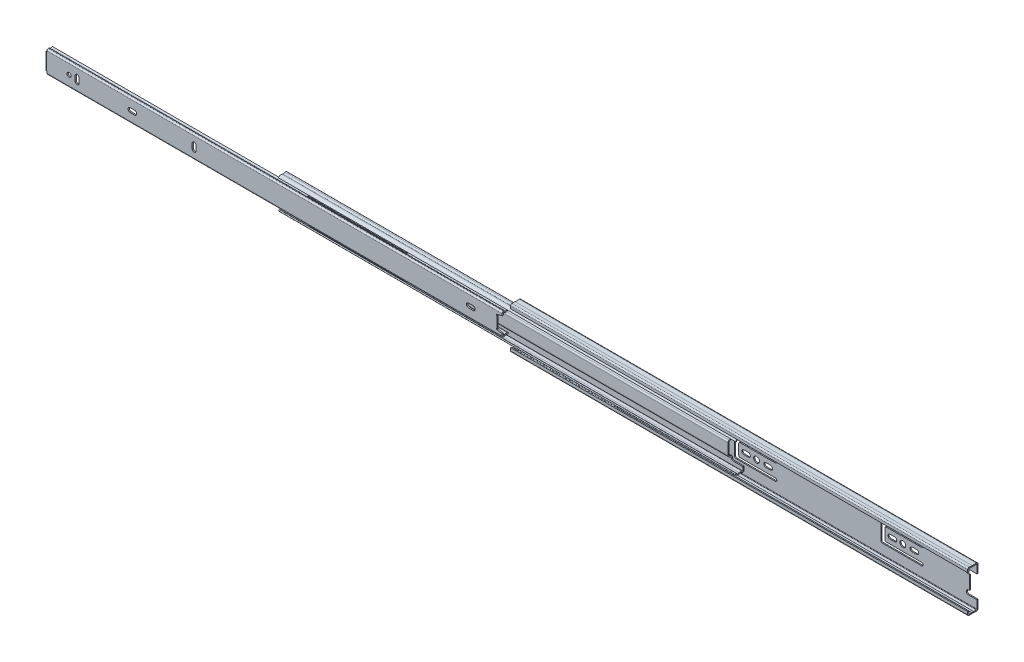
SolidWorks part; units mm, degrees
ref_plane "Front" through (0, 0, 0) normal (0, 0, 1) x (1, 0, 0)
ref_plane "Top" through (0, 0, 0) normal (0, 1, 0) x (1, 0, 0)
ref_plane "Right" through (0, 0, 0) normal (1, 0, 0) x (0, 0, -1)
sketch "Sketch1" plane through (0, 0, 0) normal (1, 0, 0) x (0, 0, -1)
  line L1 (5.6388, 0) -> (-5.6388, 0) construction
  line L4 (-4.1393, 22.8203) -> (-0.7433, 22.6989)
  line L5 (-1.1312, 21.5182) -> (-4.1819, 21.6273)
  line L6 (-4.445, 18.415) -> (-5.6388, 18.415)
  line L7 (-4.445, 21.3734) -> (-4.445, 18.415)
  line L8 (-5.6388, 18.415) -> (-5.6388, 21.3734)
  line L9 (3.9237, 21.6269) -> (0.7619, 21.5441)
  line L10 (5.6388, 0) -> (5.6388, 21.1191)
  line L11 (4.445, 21.1191) -> (4.445, 0)
  line L12 (5.6388, 0) -> (4.445, 0)
  line L13 (-0.7433, 22.6989) -> (3.8925, 22.8203)
  arc A0 (-4.445, 21.3734) -> (-4.1819, 21.6273) centre (-4.191, 21.3734) cw
  arc A1 (-5.6388, 21.3734) -> (-4.1393, 22.8203) centre (-4.191, 21.3734) cw
  arc A3 (3.9237, 21.6269) -> (4.445, 21.1191) centre (3.937, 21.1191) cw
  arc A4 (3.8925, 22.8203) -> (5.6388, 21.1191) centre (3.937, 21.1191) cw
  arc A5 (-1.1312, 21.5182) -> (0.7619, 21.5441) centre (-0.1524, 19.1744) cw
  dimension "D2" = 19.1744
  dimension "D7" = 0.254
  dimension "D8" = 0.508
  dimension "D6" = 2.54
  dimension "D9" = 1.1938
  dimension "D10" = 88.5
  dimension "D1" = 11.2776
  dimension "D3" = 5.7912
  dimension "D4" = 36.83
  dimension "D5" = 1.1938
  dimension "D11" = 87.953
  dimension "D12" = 45.6406
extrude "Extrude1" add sketch "Sketch1" along normal mid plane 500.126
ref_plane "Travel / 2" through (-504.063, 0, 0) normal (-1, 0, 0) x (0, 0, 1)
sketch "Sketch2" plane through (-504.063, 0, 0) normal (-1, 0, 0) x (0, 0, 1)
  line L0 (0.0254, 6.1159) -> (0.0254, 0)
  line L2 (-5.6388, 0) -> (5.6388, 0) construction
  line L3 (5.6388, 21.3734) -> (5.6388, 18.415) construction
  line L7 (-4.445, 21.1191) -> (-4.445, 0) construction
  line L8 (-5.6388, 0) -> (-5.6388, 21.1191) construction
  line L13 (-3.5306, 16.3766) -> (-3.5306, 9.5217)
  line L46 (-2.3867, 7.7262) -> (-0.4146, 6.8065)
  arc A0 (0.0254, 6.1159) -> (-0.4146, 6.8065) centre (-0.7366, 6.1159) ccw
  arc A1 (-1.5056, 17.2916) -> (1.2415, 16.9143) centre (0.1524, 19.1744) ccw
  arc A4 (1.1312, 21.5182) -> (-0.7619, 21.5441) centre (0.1524, 19.1744) ccw construction
  arc A19 (-3.5306, 9.5217) -> (-2.3867, 7.7262) centre (-1.5494, 9.5217) ccw
  arc A25 (-1.5056, 17.2916) -> (-3.5306, 16.3766) centre (-2.3114, 16.3766) ccw
  arc A51 (5.7404, 15.6277) -> (1.2415, 16.9143) centre (2.7686, 13.7451) ccw
  dimension "D2" = 8.4074
  dimension "D3" = 27.4903
  dimension "D6" = 1.9812
  dimension "D8" = 12.2319
  dimension "D10" = 2.5088
  dimension "D11" = 1.2192
  dimension "D4" = 0.762
  dimension "D5" = 4.4704
  dimension "D7" = 115
  dimension "D9" = 19.0435
  dimension "D13" = 11.3792
extrude "Middle Member" add sketch "Sketch2" against normal blind 500.126 separate body thin thin type one direction reverse wall 1.2192
ref_plane "Travel" through (-758.063, 0, 0) normal (-1, 0, 0) x (0, 0, 1)
sketch "Sketch3" plane through (-758.063, 0, 0) normal (-1, 0, 0) x (0, 0, 1)
  line L0 (1.2446, 0) -> (0.0254, 0) construction
  line L1 (-5.6388, 0) -> (-5.6388, 21.1191) construction
  line L56 (7.0612, 0) -> (7.0612, 10.6235)
  line L93 (5.5372, 12.1475) -> (5.1643, 12.1475)
  arc A0 (1.2082, 11.9072) -> (4.2365, 11.8325) centre (2.7686, 13.7451) ccw
  arc A29 (7.0612, 10.6235) -> (5.5372, 12.1475) centre (5.5372, 10.6235) ccw
  arc A53 (5.1643, 12.1475) -> (4.2365, 11.8325) centre (5.1643, 10.6235) ccw
  dimension "D1" = 1.524
  dimension "D4" = 1.524
  dimension "D5" = 2.411
  dimension "D2" = 12.7
  dimension "D3" = 12.1475
  dimension "D6" = 5.853
extrude "Drawer Member" add sketch "Sketch3" against normal blind 500.126 thin thin type one direction wall 1.397
sketch "Sketch6" plane through (0, 0, 7.0612) normal (0, 0, 1) x (1, 0, 0)
  line L1 (-758.063, 0) -> (-756.158, 0)
  line L2 (-758.063, 0) -> (-758.063, 12.1475)
  line L3 (-758.063, 12.1475) -> (-756.158, 12.1475)
  line L4 (-756.158, 0) -> (-756.158, 12.1475)
  line L5 (-257.937, 12.1475) -> (-758.063, 12.1475) construction
  line L7 (-758.063, 10.6235) -> (-758.063, 0) construction
  line L8 (-257.937, 0) -> (-758.063, 0) construction
  dimension "D1" = 1.905
extrude "Cut-Extrude1" cut sketch "Sketch6" against normal through all
sketch "Sketch7" plane through (0, 0, 0) normal (0, -1, 0) x (1, 0, 0)
  line L0 (-756.158, 7.0612) -> (-756.412, 7.0612)
  line L1 (-758.063, 5.4102) -> (-758.063, 0.3041)
  line L2 (-758.063, 0.3041) -> (-756.666, 0.3041)
  line L3 (-756.666, 0.3041) -> (-756.666, 5.4102)
  line L4 (-756.412, 5.6642) -> (-756.158, 5.6642)
  line L5 (-257.937, 5.6642) -> (-756.158, 5.6642) construction
  line L6 (-756.158, 7.0612) -> (-756.158, 5.6642)
  line L7 (-257.937, 0.3041) -> (-756.158, 0.3041) construction
  line L9 (-756.158, 5.087) -> (-756.158, 0.3041) construction
  arc A0 (-756.412, 5.6642) -> (-756.666, 5.4102) centre (-756.412, 5.4102) ccw
  arc A1 (-756.412, 7.0612) -> (-758.063, 5.4102) centre (-756.412, 5.4102) ccw
  dimension "D1" = 0.254
  dimension "D2" = 1.905
extrude "Extrude4" add sketch "Sketch7" against normal blind 8.89
sketch "Sketch8" plane through (0, 0, -4.445) normal (0, 0, 1) x (1, 0, 0)
  line L0 (240.4245, 7.6456) -> (241.8588, 7.493)
  line L1 (250.063, 12.2048) -> (240.6664, 12.2048)
  line L2 (241.8588, 7.493) -> (241.8588, 0)
  line L3 (250.063, 0) -> (-250.063, 0) construction
  line L4 (250.063, 21.1191) -> (250.063, 0) construction
  line L5 (250.063, 12.2048) -> (250.063, 0)
  line L6 (250.063, 0) -> (241.8588, 0)
  arc A0 (240.6664, 12.2048) -> (240.4245, 7.6456) centre (240.6664, 9.9188) ccw
  dimension "D3" = 9.9188
  dimension "D1" = 12.2048
  dimension "D2" = 8.2042
  dimension "D4" = 9.3966
  dimension "D5" = 7.493
extrude "Cut-Extrude2" cut sketch "Sketch8" against normal up to next (1.1938 mm away)
sketch "Sketch11" plane through (0, 0, 7.0612) normal (0, 0, 1) x (1, 0, 0)
  line L0 (-263.652, 5.9678) -> (-263.652, 0)
  line L8 (-257.937, 8.5893) -> (-263.7963, 7.2212)
  line L11 (-263.652, 0) -> (-257.937, 0)
  line L12 (-257.937, 0) -> (-257.937, 8.5893)
  arc A1 (-263.7963, 7.2212) -> (-263.652, 5.9678) centre (-263.6519, 6.6028) ccw
  dimension "D3" = 0.635
  dimension "D1" = 5.715
  dimension "D2" = 8.5893
  dimension "D4" = 5.9678
  dimension "D5" = 103.143
extrude "Cut-Extrude3" cut sketch "Sketch11" against normal up to next (1.397 mm away)
sketch "Sketch12" plane through (0, 0, 1.2446) normal (0, 0, 1) x (1, 0, 0)
  line L0 (-3.937, 12.065) -> (-14.097, 12.065)
  line L1 (-3.937, 16.3766) -> (-3.937, 9.5217) construction
  line L2 (-16.637, 9.525) -> (-16.637, 0)
  line L3 (-3.937, 0) -> (-504.063, 0) construction
  line L4 (-16.637, 0) -> (-3.937, 0)
  line L5 (-3.937, 0) -> (-3.937, 12.065)
  arc A0 (-14.097, 12.065) -> (-16.637, 9.525) centre (-14.097, 9.525) ccw
  point P11 (-16.637, 12.065)
  dimension "D3" = 2.54
  dimension "D1" = 12.7
  dimension "D2" = 12.065
extrude "Cut-Extrude4" cut sketch "Sketch12" against normal through all
sketch "Sketch13" plane through (0, 0, -4.445) normal (0, 0, 1) x (1, 0, 0)
  line L0 (-181.6747, 7.112) -> (-206.5032, 7.112)
  line L1 (241.8588, 0) -> (-250.063, 0) construction
  line L2 (-189.7646, 0) -> (-189.7646, 4.2392) construction
  line L3 (-232.6017, 10.287) -> (-181.6747, 10.287)
  line L4 (-250.063, 21.1191) -> (-250.063, 0) construction
  line L5 (-210.3132, 7.112) -> (-232.6017, 7.112)
  line L6 (-209.5512, 0) -> (-209.5512, 6.35)
  line L7 (-207.2652, 6.35) -> (-207.2652, 0)
  line L8 (-187.2881, 2.286) -> (-192.2411, 2.286)
  line L13 (-226.3406, 0) -> (-221.7686, 0)
  line L14 (-218.238, 0) -> (-211.888, 0)
  line L15 (-209.5512, 0) -> (-207.2652, 0)
  line L16 (-204.7506, 0) -> (-200.1786, 0)
  line L17 (-194.5271, 0) -> (-185.0021, 0)
  arc A1 (-232.6017, 10.287) -> (-232.6017, 7.112) centre (-232.6017, 8.6995) ccw
  arc A2 (-209.5512, 6.35) -> (-210.3132, 7.112) centre (-210.3132, 6.35) ccw
  arc A4 (-206.5032, 7.112) -> (-207.2652, 6.35) centre (-206.5032, 6.35) ccw
  arc A7 (-181.6747, 7.112) -> (-181.6747, 10.287) centre (-181.6747, 8.6995) ccw
  arc A8 (-211.888, 0) -> (-218.238, 0) centre (-215.063, 0) ccw
  arc A9 (-221.7686, 0) -> (-226.3406, 0) centre (-224.0546, 0) ccw
  arc A10 (-200.1786, 0) -> (-204.7506, 0) centre (-202.4646, 0) ccw
  arc A11 (-185.0021, 0) -> (-187.2881, 2.286) centre (-187.2881, 0) ccw
  arc A12 (-192.2411, 2.286) -> (-194.5271, 0) centre (-192.2411, 0) ccw
  dimension "D3" = 2.286
  dimension "D4" = 3.175
  dimension "D7" = 8.9916
  dimension "D8" = 21.59
  dimension "D9" = 34.29
  dimension "D10" = 0.762
  dimension "D11" = 17.5387
  dimension "D12" = 9.525
  dimension "D13" = 5.5118
  dimension "D14" = 35
  dimension "D1" = 3.175
  dimension "D2" = 50.927
  dimension "D5" = 2.286
  dimension "D6" = 10.287
extrude "Cut-Extrude5" cut sketch "Sketch13" against normal up to next (1.1938 mm away)
sketch "Sketch32" plane through (0, 0, -5.6388) normal (0, 0, -1) x (-1, 0, 0)
  line L0 (69.6005, 0) -> (79.1255, 0)
  line L1 (83.888, 0) -> (90.238, 0)
  line L2 (93.7305, 0) -> (103.2555, 0)
  line L3 (106.621, 0) -> (111.193, 0)
  line L4 (-241.8588, 0) -> (185.0021, 0) construction
  line L5 (232.6017, 10.287) -> (181.6747, 10.287) construction
  line L6 (181.6747, 7.112) -> (206.5032, 7.112) construction
  line L7 (98.493, 2.286) -> (98.493, -3.4269) construction
  line L8 (74.363, 2.286) -> (74.363, -3.4269) construction
  line L14 (66.4255, 10.287) -> (109.669, 10.287)
  line L15 (105.097, 7.112) -> (66.4255, 7.112)
  line L17 (111.193, 8.763) -> (111.193, 0)
  line L18 (106.621, 0) -> (106.621, 5.588)
  line L23 (71.8865, 2.286) -> (76.8395, 2.286)
  line L25 (96.0165, 2.286) -> (100.9695, 2.286)
  arc A0 (218.238, 0) -> (211.888, 0) centre (215.063, 0) ccw construction
  arc A13 (111.193, 8.763) -> (109.669, 10.287) centre (109.669, 8.763) ccw
  arc A14 (106.621, 5.588) -> (105.097, 7.112) centre (105.097, 5.588) ccw
  arc A17 (66.4255, 10.287) -> (66.4255, 7.112) centre (66.4255, 8.6995) ccw
  arc A20 (79.1255, 0) -> (76.8395, 2.286) centre (76.8395, 0) ccw
  arc A21 (71.8865, 2.286) -> (69.6005, 0) centre (71.8865, 0) ccw
  arc A22 (90.238, 0) -> (83.888, 0) centre (87.063, 0) ccw
  arc A24 (103.2555, 0) -> (100.9695, 2.286) centre (100.9695, 0) ccw
  arc A25 (96.0165, 2.286) -> (93.7305, 0) centre (96.0165, 0) ccw
  dimension "D2" = 1.524
  dimension "D3" = 3.175
  dimension "D4" = 9.525
  dimension "D5" = 2.286
  dimension "D6" = 11.43
  dimension "D7" = 12.7
  dimension "D8" = 24.13
  dimension "D9" = 20.6375
  dimension "D10" = 128
  dimension "D1" = 4.572
extrude "Cut-Extrude14" cut sketch "Sketch32" against normal up to next (1.1938 mm away)
sketch "Sketch33" plane through (83.6094, 0.8125, -5.6388) normal (0, 0, -1) x (-1, 0, 0)
  line L0 (57.2099, -0.8125) -> (66.7349, -0.8125)
  line L1 (71.4974, -0.8125) -> (77.8474, -0.8125)
  line L2 (81.3399, -0.8125) -> (90.8649, -0.8125)
  line L3 (94.2304, -0.8125) -> (98.8024, -0.8125)
  line L7 (86.1024, 1.4735) -> (86.1024, -4.2394) construction
  line L8 (61.9724, 1.4735) -> (61.9724, -3.4269) construction
  line L9 (-158.2494, -0.8125) -> (153.2099, -0.8125) construction
  line L10 (193.2784, 9.4745) -> (150.0349, 9.4745) construction
  line L11 (150.0349, 6.2995) -> (188.7064, 6.2995) construction
  line L14 (54.0349, 9.4745) -> (97.2784, 9.4745)
  line L15 (92.7064, 6.2995) -> (54.0349, 6.2995)
  line L17 (98.8024, 7.9505) -> (98.8024, -0.8125)
  line L18 (94.2304, -0.8125) -> (94.2304, 4.7755)
  line L23 (59.4959, 1.4735) -> (64.4489, 1.4735)
  line L25 (83.6259, 1.4735) -> (88.5789, 1.4735)
  arc A1 (301.8474, -0.8125) -> (295.4974, -0.8125) centre (298.6724, -0.8125) ccw construction
  arc A13 (98.8024, 7.9505) -> (97.2784, 9.4745) centre (97.2784, 7.9505) ccw
  arc A14 (94.2304, 4.7755) -> (92.7064, 6.2995) centre (92.7064, 4.7755) ccw
  arc A17 (54.0349, 9.4745) -> (54.0349, 6.2995) centre (54.0349, 7.887) ccw
  arc A20 (66.7349, -0.8125) -> (64.4489, 1.4735) centre (64.4489, -0.8125) ccw
  arc A21 (59.4959, 1.4735) -> (57.2099, -0.8125) centre (59.4959, -0.8125) ccw
  arc A22 (77.8474, -0.8125) -> (71.4974, -0.8125) centre (74.6724, -0.8125) ccw
  arc A24 (90.8649, -0.8125) -> (88.5789, 1.4735) centre (88.5789, -0.8125) ccw
  arc A25 (83.6259, 1.4735) -> (81.3399, -0.8125) centre (83.6259, -0.8125) ccw
  dimension "D2" = 1.524
  dimension "D3" = 3.175
  dimension "D4" = 9.525
  dimension "D5" = 2.286
  dimension "D6" = 11.43
  dimension "D7" = 12.7
  dimension "D8" = 24.13
  dimension "D9" = 20.6375
  dimension "D10" = 224
  dimension "D1" = 4.572
extrude "Cut-Extrude6" cut sketch "Sketch33" against normal up to next (1.1938 mm away)
sketch "Sketch34" plane through (169.8236, 1.4527, -5.6388) normal (0, 0, -1) x (-1, 0, 0)
  line L0 (-16.6239, -1.4527) -> (-7.0989, -1.4527)
  line L1 (-2.3364, -1.4527) -> (4.0136, -1.4527)
  line L2 (7.5061, -1.4527) -> (17.0311, -1.4527)
  line L3 (20.3966, -1.4527) -> (24.9686, -1.4527)
  line L4 (-72.0352, -1.4527) -> (143.4241, -1.4527) construction
  line L7 (12.2686, 0.8333) -> (12.2686, -4.8796) construction
  line L8 (-11.8614, 0.8333) -> (-11.8614, -4.0671) construction
  line L9 (279.4926, 8.8343) -> (236.2491, 8.8343) construction
  line L10 (236.2491, 5.6593) -> (274.9206, 5.6593) construction
  line L14 (-19.7989, 8.8343) -> (23.4446, 8.8343)
  line L15 (18.8726, 5.6593) -> (-19.7989, 5.6593)
  line L17 (24.9686, 7.3103) -> (24.9686, -1.4527)
  line L18 (20.3966, -1.4527) -> (20.3966, 4.1353)
  line L23 (-14.3379, 0.8333) -> (-9.3849, 0.8333)
  line L25 (9.7921, 0.8333) -> (14.7451, 0.8333)
  arc A0 (388.0616, -1.4527) -> (381.7116, -1.4527) centre (384.8866, -1.4527) ccw construction
  arc A13 (24.9686, 7.3103) -> (23.4446, 8.8343) centre (23.4446, 7.3103) ccw
  arc A14 (20.3966, 4.1353) -> (18.8726, 5.6593) centre (18.8726, 4.1353) ccw
  arc A17 (-19.7989, 8.8343) -> (-19.7989, 5.6593) centre (-19.7989, 7.2468) ccw
  arc A20 (-7.0989, -1.4527) -> (-9.3849, 0.8333) centre (-9.3849, -1.4527) ccw
  arc A21 (-14.3379, 0.8333) -> (-16.6239, -1.4527) centre (-14.3379, -1.4527) ccw
  arc A22 (4.0136, -1.4527) -> (-2.3364, -1.4527) centre (0.8386, -1.4527) ccw
  arc A24 (17.0311, -1.4527) -> (14.7451, 0.8333) centre (14.7451, -1.4527) ccw
  arc A25 (9.7921, 0.8333) -> (7.5061, -1.4527) centre (9.7921, -1.4527) ccw
  dimension "D2" = 1.524
  dimension "D3" = 3.175
  dimension "D4" = 9.525
  dimension "D5" = 2.286
  dimension "D6" = 11.43
  dimension "D7" = 12.7
  dimension "D8" = 24.13
  dimension "D9" = 20.6375
  dimension "D10" = 384.048
  dimension "D1" = 4.572
extrude "Cut E" cut sketch "Sketch34" against normal up to next (1.1938 mm away)
sketch "Sketch24" plane through (0, 0, 7.0612) normal (0, 0, 1) x (1, 0, 0)
  line L0 (-263.652, 0) -> (-756.412, 0) construction
  line L1 (-723.011, 4.826) -> (-723.011, 0) construction
  line L2 (-725.1954, 2.6416) -> (-725.1954, 0)
  line L3 (-725.1954, 0) -> (-720.8266, 0)
  line L4 (-720.8266, 0) -> (-720.8266, 2.6416)
  line L5 (-667.3215, 0) -> (-657.7965, 0)
  line L6 (-665.0355, 2.286) -> (-660.0825, 2.286)
  line L8 (-597.1954, 2.6416) -> (-597.1954, 0)
  line L9 (-597.1954, 0) -> (-592.8266, 0)
  line L10 (-592.8266, 0) -> (-592.8266, 2.6416)
  line L11 (-758.063, 8.89) -> (-758.063, 0) construction
  line L12 (-662.559, 2.286) -> (-662.559, 0) construction
  circle A0 centre (-731.901, 0) radius 2.1844
  arc A1 (-725.1954, 2.6416) -> (-720.8266, 2.6416) centre (-723.011, 2.6416) cw
  arc A2 (-667.3215, 0) -> (-665.0355, 2.286) centre (-665.0355, 0) cw
  arc A3 (-660.0825, 2.286) -> (-657.7965, 0) centre (-660.0825, 0) cw
  arc A4 (-597.1954, 2.6416) -> (-592.8266, 2.6416) centre (-595.011, 2.6416) cw
  dimension "D1" = 4.3688
  dimension "D4" = 8.89
  dimension "D5" = 2.286
  dimension "D7" = 60.452
  dimension "D8" = 128
  dimension "D2" = 35.052
  dimension "D3" = 4.826
  dimension "D6" = 9.525
extrude "Cut-Extrude13" cut sketch "Sketch24" against normal up to next (1.397 mm away)
sketch "Sketch25" plane through (0, 0, 7.0612) normal (0, 0, 1) x (1, 0, 0)
  line L1 (-263.652, 0) -> (-592.8266, 0) construction
  line L5 (-287.4645, 0) -> (-296.9895, 0)
  line L6 (-660.0825, 2.286) -> (-665.0355, 2.286) construction
  line L7 (-294.7035, 2.286) -> (-289.7505, 2.286)
  line L8 (-292.227, 0) -> (-292.227, 2.286) construction
  arc A1 (-720.8266, 2.6416) -> (-725.1954, 2.6416) centre (-723.011, 2.6416) ccw construction
  arc A3 (-294.7035, 2.286) -> (-296.9895, 0) centre (-294.7035, 0) ccw
  arc A4 (-289.7505, 2.286) -> (-287.4645, 0) centre (-289.7505, 0) cw
  arc A5 (-657.7965, 0) -> (-660.0825, 2.286) centre (-660.0825, 0) ccw construction
  dimension "D1" = 430.784
extrude "Cut D" cut sketch "Sketch25" against normal up to next (1.397 mm away)
sketch "Sketch36" plane through (0, 0, 7.0612) normal (0, 0, 1) x (1, 0, 0)
  line L0 (-309.1954, 0) -> (-304.8266, 0)
  line L1 (-304.8266, 0) -> (-304.8266, 2.6416)
  line L2 (-309.1954, 2.6416) -> (-309.1954, 0)
  line L4 (-296.9895, 0) -> (-592.8266, 0) construction
  line L5 (-720.8266, 0) -> (-720.8266, 2.6416) construction
  arc A0 (-304.8266, 2.6416) -> (-309.1954, 2.6416) centre (-307.011, 2.6416) ccw
  circle A1 centre (-319.711, 0) radius 2.1844
  arc A5 (-720.8266, 2.6416) -> (-725.1954, 2.6416) centre (-723.011, 2.6416) ccw construction
  dimension "D1" = 4.3688
  dimension "D2" = 416
  dimension "D3" = 12.7
extrude "Cut B" [suppressed] cut sketch "Sketch36" against normal up to next
sketch "Sketch38" plane through (0, 0, 7.0612) normal (0, 0, 1) x (1, 0, 0)
  line L0 (-501.1954, 0) -> (-501.1954, 2.6416)
  line L1 (-296.9895, 0) -> (-592.8266, 0) construction
  line L2 (-496.8266, 2.6416) -> (-496.8266, 0)
  line L3 (-496.8266, 0) -> (-501.1954, 0)
  line L4 (-720.8266, 0) -> (-720.8266, 2.6416) construction
  line L5 (-492.28, 0) -> (-484.406, 0)
  line L6 (-492.28, 0) -> (-492.28, 2.3749)
  line L7 (-492.28, 2.3749) -> (-484.406, 2.3749)
  line L8 (-484.406, 0) -> (-484.406, 2.3749)
  line L9 (-499.011, 7.182) -> (-499.011, -4.0911) construction
  line L10 (-505.742, 0) -> (-513.616, 0)
  line L11 (-505.742, 0) -> (-505.742, 2.3749)
  line L12 (-505.742, 2.3749) -> (-513.616, 2.3749)
  line L13 (-513.616, 0) -> (-513.616, 2.3749)
  line L14 (-488.343, 2.3749) -> (-488.343, -3.2385) construction
  arc A0 (-501.1954, 2.6416) -> (-496.8266, 2.6416) centre (-499.011, 2.6416) cw
  arc A1 (-720.8266, 2.6416) -> (-725.1954, 2.6416) centre (-723.011, 2.6416) ccw construction
  dimension "D4" = 224
  dimension "D1" = 7.874
  dimension "D2" = 2.3749
  dimension "D3" = 10.668
extrude "Cut A" [suppressed] cut sketch "Sketch38" against normal up to next
ref_plane "Plane3" through (-237.363, 0, 0) normal (-1, 0, 0) x (0, 0, 1)
sketch "Sketch27" plane through (-237.363, 0, 0) normal (-1, 0, 0) x (0, 0, 1)
  line L0 (0.1524, 21.6832) -> (0.1524, 16.6656)
  line L1 (0.1524, 23.635) -> (0.1524, 15.2838) construction
  arc A0 (0.1524, 16.6656) -> (0.1524, 21.6832) centre (0.1524, 19.1744) ccw
  arc A1 (-1.5056, 17.2916) -> (1.2415, 16.9143) centre (0.1524, 19.1744) ccw construction
revolve "Revolve1" add sketch "Sketch27" angle 360 about L1
pattern_linear "LPattern1" count 6 spacing 19.05 along (1, 0, 0) of bodies 128
sketch "Sketch28" plane through (-237.363, 0, 0) normal (-1, 0, 0) x (0, 0, 1)
  line L0 (2.6612, 19.1744) -> (-2.3564, 19.1744) construction
  line L1 (3.9624, 18.7934) -> (-3.6576, 18.7934)
  line L2 (3.9624, 18.7934) -> (3.9624, 19.5554)
  line L3 (3.9624, 19.5554) -> (-3.6576, 19.5554)
  line L4 (-3.6576, 18.7934) -> (-3.6576, 19.5554)
  line L5 (0.1524, 20.5465) -> (0.1524, 17.804) construction
  circle A1 centre (0.1524, 19.1744) radius 2.5088 construction
  point P8 (0.1524, 19.1744)
  dimension "D1" = 7.62
  dimension "D2" = 0.762
extrude "Extrude7" add sketch "Sketch28" along normal blind 6.35 and the other way blind 101.6
ref_plane "Plane4" through (-465.963, 0, 0) normal (-1, 0, 0) x (0, 0, 1)
sketch "Sketch29" plane through (-465.963, 0, 0) normal (-1, 0, 0) x (0, 0, 1)
  line L0 (2.7686, 16.0438) -> (2.7686, 11.4464)
  line L1 (2.7686, 16.6801) -> (2.7686, 10.2973) construction
  arc A0 (2.7686, 11.4464) -> (2.7686, 16.0438) centre (2.7686, 13.7451) ccw
  arc A1 (4.7105, 14.9753) -> (1.7707, 15.816) centre (2.7686, 13.7451) ccw construction
revolve "Revolve2" add sketch "Sketch29" angle 360 about L1
pattern_linear "LPattern2" count 6 spacing 19.05 along (1, 0, 0) of bodies 135
sketch "Sketch30" plane through (-465.963, 0, 0) normal (-1, 0, 0) x (0, 0, 1)
  line L0 (0.4699, 13.7451) -> (5.0673, 13.7451) construction
  line L1 (3.9624, 18.7934) -> (3.9624, 19.5554) construction
  line L2 (0.2286, 14.1261) -> (5.3086, 14.1261)
  line L3 (0.2286, 14.1261) -> (0.2286, 13.3641)
  line L4 (0.2286, 13.3641) -> (5.3086, 13.3641)
  line L5 (5.3086, 14.1261) -> (5.3086, 13.3641)
  line L7 (2.7686, 14.2437) -> (2.7686, 12.7853) construction
  circle A0 centre (2.7686, 13.7451) radius 2.2987 construction
  point P4 (2.7686, 13.7451)
  dimension "D1" = 5.08
extrude "Extrude8" add sketch "Sketch30" along normal blind 6.35 and the other way blind 101.6
mirror "Mirror3" about plane through (0, 0, 0) normal (0, 1, 0) of bodies 126 119 164 117 124 127 159
mirror "Mirror5" about plane through (0, 0, 0) normal (0, 1, 0) of bodies 141 134
ref_plane "Plane5" through (184.1615, 2.286, -5.6388) normal (1, 0, 0) x (0, 0, -1)
ref_plane "Plane6" through (184.1615, 2.286, -4.445) normal (-1, 0, 0) x (0, 0, 1)
sketch "Sketch41" plane through (0, 0, -5.6388) normal (0, 0, 1) x (1, 0, 0)
  line L0 (181.685, 2.286) -> (181.685, -2.286) construction
  line L1 (179.2085, 2.286) -> (184.1615, 2.286) construction
  line L2 (179.2085, -2.286) -> (184.1615, -2.286) construction
  line L3 (186.4475, 0) -> (176.9225, 0) construction
  arc A0 (184.1615, -2.286) -> (184.1615, 2.286) centre (184.1615, 0) ccw construction
  arc A1 (179.2085, 2.286) -> (179.2085, -2.286) centre (179.2085, 0) ccw construction
ref_plane "Plane7" through (-187.2881, -2.286, -5.6388) normal (1, 0, 0) x (0, 0, -1)
ref_plane "Plane8" through (-192.2411, 2.286, -5.6388) normal (1, 0, 0) x (0, 0, -1)
sketch "Sketch42" plane through (0, 0, -5.6388) normal (0, 0, -1) x (-1, 0, 0)
  line L0 (-250.063, 12.2048) -> (-250.063, -12.2048)
  line L1 (-250.063, 0) -> (-241.8588, 0)
  line L2 (-241.8588, -7.493) -> (-241.8588, 7.493) construction
